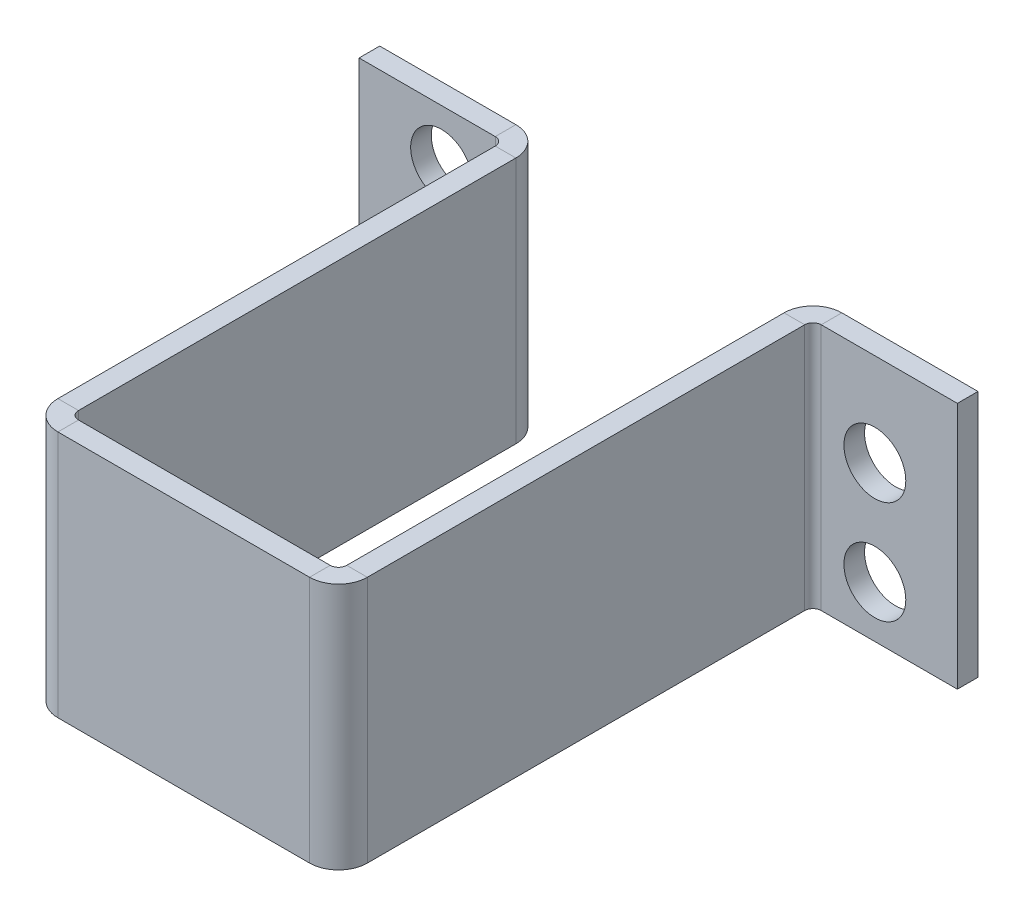
SolidWorks part; units mm, degrees
note: The reader was unsure of these and kept them because the rebuilt part matched: flange length of "Bordo-Flangia1", "Bordo-Flangia2".
ref_plane "Piano frontale" through (0, 0, 0) normal (0, 0, 1) x (1, 0, 0)
ref_plane "Piano superiore" through (0, 0, 0) normal (0, 1, 0) x (1, 0, 0)
ref_plane "Piano destro" through (0, 0, 0) normal (1, 0, 0) x (0, 0, -1)
sketch "Schizzo1" plane through (0, 0, 0) normal (0, 0, 1) x (1, 0, 0)
  line L1 (3.25, -3) -> (-3.25, -3)
  line L2 (3.25, -3) -> (3.25, 3)
  line L3 (3.25, 3) -> (-3.25, 3)
  line L4 (-3.25, -3) -> (-3.25, 3)
  line L5 (3.25, -3) -> (-3.25, 3) construction
  line L6 (3.25, 3) -> (-3.25, -3) construction
  point P0 (0, 0)
  dimension "D1" = 6
  dimension "D2" = 6.5
base flange "Base-Flangia1" sketch "Schizzo1" thickness 0.5 reverse thickness direction no parameters "D1"=0.7366
edge flange "Bordo-Flangia1" sketch "Schizzo10" flange profiles "Schizzo10", "Schizzo11" flange angle 90 flange length 11.5 flange position material outside bend radius 0.2 thickness 0.5 relief rectangular parameters "D6"=10, "D8"=1
sketch "Schizzo10" plane through (-3.25, 0, -0.5) normal (-1, 0, 0) x (0, 1, 0)
  line L0 (3, 0) -> (-3, 0) construction
  line L1 (3, 0) -> (-3, 0)
  line L2 (-3, 0) -> (-3, 11)
  line L3 (-3, 11) -> (3, 11)
  line L4 (3, 11) -> (3, 0)
sketch "Schizzo11" plane through (3.25, 0, -0.5) normal (1, 0, 0) x (0, -1, 0)
  line L0 (3, 0) -> (-3, 0) construction
  line L1 (3, 0) -> (-3, 0)
  line L2 (-3, 0) -> (-3, 11)
  line L3 (-3, 11) -> (3, 11)
  line L4 (3, 11) -> (3, 0)
bend "PiegaturaBordo1" bend radius 0.2 bend angle 90 parameters "D5"=1
bend "PiegaturaBordo2" bend radius 0.2 bend angle 90 parameters "D5"=2
edge flange "Bordo-Flangia2" sketch "Schizzo16" flange profiles "Schizzo16", "Schizzo17" flange angle 90 flange length 4 flange position material outside bend radius 0.2 thickness 0.5 relief rectangular parameters "D6"=10, "D8"=1
sketch "Schizzo16" plane through (-3.75, 0, -11.5) normal (0, 0, -1) x (0, -1, 0)
  line L0 (-3, 0) -> (3, 0) construction
  line L1 (-3, 0) -> (3, 0)
  line L2 (-3, 0) -> (-3, 3.5)
  line L3 (-3, 3.5) -> (3, 3.5)
  line L4 (3, 3.5) -> (3, 0)
sketch "Schizzo17" plane through (3.75, 0, -11.5) normal (0, 0, -1) x (0, 1, 0)
  line L0 (-3, 0) -> (3, 0) construction
  line L1 (-3, 0) -> (3, 0)
  line L2 (-3, 0) -> (-3, 3.5)
  line L3 (-3, 3.5) -> (3, 3.5)
  line L4 (3, 3.5) -> (3, 0)
bend "PiegaturaBordo3" bend radius 0.2 bend angle 90 parameters "D5"=3
bend "PiegaturaBordo4" bend radius 0.2 bend angle 90 parameters "D5"=4
sketch "Schizzo18" plane through (0, 0, -11.5) normal (0, 0, 1) x (1, 0, 0)
  line L0 (5.25, 3) -> (5.25, -3) construction
  line L4 (7.25, 3) -> (7.25, -3) construction
  line L5 (7.25, -3) -> (3.95, -3) construction
  circle A0 centre (5.25, 0.75) radius 0.75
  circle A1 centre (5.25, -1.75) radius 0.75
  point P2 (0, 0)
  point P5 (5.25, 1.3954)
  point P10 (0, 0)
  point P12 (0, 0)
  dimension "D1" = 1.5
  dimension "D2" = 1.5
  dimension "D3" = 1.25
  dimension "D4" = 2.5
  dimension "D5" = 2
extrude "Taglio-Estrusione1" cut sketch "Schizzo18" against normal through all normal cut yes
sketch "Schizzo22" plane through (0, 0, -11.5) normal (0, 0, 1) x (1, 0, 0)
  line L0 (-5.25, 3) -> (-5.25, -3) construction
  line L1 (-7.25, 3) -> (-3.95, 3) construction
  line L2 (-3.95, -3) -> (-7.25, -3) construction
  line L3 (-7.25, -3) -> (-7.25, 3) construction
  circle A0 centre (-5.25, 1.75) radius 0.75
  circle A1 centre (-5.25, -0.75) radius 0.75
  dimension "D2" = 1.5
  dimension "D3" = 1.5
  dimension "D1" = 2
  dimension "D4" = 2.25
  dimension "D5" = 2.5
extrude "Taglio-Estrusione2" cut sketch "Schizzo22" against normal through all normal cut yes
sketch "Linee di piegatura1" [suppressed] plane through (0, 0, 0) normal (0, 1, 0) x (1, 0, 0)
sketch "Casella di contorno1" [suppressed] plane through (0, 0, 0) normal (0, 1, 0) x (1, 0, 0)
sheet metal parameters "Lamiera1" thickness 0.5 parameters "D1"=0.7366
flat pattern "Ripetizione piatta1" [suppressed]
sketch "Linee di piegatura2" plane through (0, 0, 0) normal (0, 1, 0) x (1, 0, 0)
sketch3d "Casella di contorno2" [suppressed]
  line L0 (3.25, -3, 0) -> (-3.25, -3, 0) construction
  line L1 (3.25, 3, 0) -> (-3.25, 3, 0) construction
  line L2 (3.25, -3, 0) -> (3.25, 3, 0) construction
  line L3 (-3.25, -3, 0) -> (-3.25, 3, 0) construction
sheet metal parameters "Lamiera2" thickness 0.5 parameters "D1"=0.7366
flat pattern "Ripetizione piatta1"
sketch "Linee di piegatura2" plane through (0, 0, 0) normal (0, 0, 1) x (1, 0, 0)
  line L0 (3.4034, -3) -> (3.4034, 3) construction
  line L1 (-3.4034, 3) -> (-3.4034, -3) construction
  line L2 (3.4034, -3) -> (3.4034, 3) construction
  line L3 (-3.4034, 3) -> (-3.4034, -3) construction
sketch3d "Casella di contorno2" [suppressed]
  line L0 (-14.5569, -3, 0) -> (14.5569, -3, 0) construction
  line L1 (-14.5569, 3, 0) -> (14.5569, 3, 0) construction
  line L2 (-14.5569, -3, 0) -> (-14.5569, 3, 0) construction
  line L3 (14.5569, -3, 0) -> (14.5569, 3, 0) construction
bend of the flat pattern "Appiattito-<PiegaturaBordo1>1"
bend of the flat pattern "Appiattito-<PiegaturaBordo2>1"
sheet metal parameters "Lamiera3" thickness 0.5 parameters "D1"=0.7366
flat pattern "Ripetizione piatta1" [suppressed]
sketch "Linee di piegatura2" plane through (0, 0, 0) normal (0, 0, 1) x (1, 0, 0)
  line L0 (3.4034, -3) -> (3.4034, 3) construction
  line L1 (-3.4034, 3) -> (-3.4034, -3) construction
  line L2 (3.4034, -3) -> (3.4034, 3) construction
  line L3 (-3.4034, 3) -> (-3.4034, -3) construction
  line L4 (14.603, -3) -> (14.603, 3) construction
  line L5 (-14.603, 3) -> (-14.603, -3) construction
  line L6 (14.603, -3) -> (14.603, 3) construction
  line L7 (-14.603, 3) -> (-14.603, -3) construction
sketch3d "Casella di contorno2" [suppressed]
  line L0 (-18.1491, -3, 0) -> (18.1491, -3, 0) construction
  line L1 (-18.1491, 3, 0) -> (18.1491, 3, 0) construction
  line L2 (-18.1491, -3, 0) -> (-18.1491, 3, 0) construction
  line L3 (18.1491, -3, 0) -> (18.1491, 3, 0) construction
bend of the flat pattern "Appiattito-<PiegaturaBordo1>1"
bend of the flat pattern "Appiattito-<PiegaturaBordo2>1"
bend of the flat pattern "Appiattito-<PiegaturaBordo3>1"
bend of the flat pattern "Appiattito-<PiegaturaBordo4>1"
sketch "Schizzo18-1" [suppressed] plane through (10.8991, 0, 0) normal (0, 0, 1) x (1, 0, 0)
  line L0 (5.25, 3) -> (5.25, -3) construction
  line L4 (7.25, 3) -> (7.25, -3) construction
  circle A0 centre (5.25, 0.75) radius 0.75
  circle A1 centre (5.25, -1.75) radius 0.75
  dimension "D1" = 1.5
  dimension "D2" = 1.5
  dimension "D3" = 1.25
  dimension "D4" = 2.5
  dimension "D5" = 2
sheet metal parameters "Lamiera4" thickness 0.5 parameters "D1"=0.7366
flat pattern "Ripetizione piatta1" [suppressed]
sketch "Linee di piegatura2" plane through (0, 0, 0) normal (0, 0, 1) x (1, 0, 0)
  line L0 (3.4034, -3) -> (3.4034, 3) construction
  line L1 (-3.4034, 3) -> (-3.4034, -3) construction
  line L2 (3.4034, -3) -> (3.4034, 3) construction
  line L3 (-3.4034, 3) -> (-3.4034, -3) construction
  line L4 (14.7103, -3) -> (14.7103, 3) construction
  line L5 (-14.7103, 3) -> (-14.7103, -3) construction
  line L6 (14.7103, -3) -> (14.7103, 3) construction
  line L7 (-14.7103, 3) -> (-14.7103, -3) construction
sketch3d "Casella di contorno2" [suppressed]
  line L0 (-18.3637, -3, 0) -> (18.3637, -3, 0) construction
  line L1 (-18.3637, 3, 0) -> (18.3637, 3, 0) construction
  line L2 (-18.3637, -3, 0) -> (-18.3637, 3, 0) construction
  line L3 (18.3637, -3, 0) -> (18.3637, 3, 0) construction
bend of the flat pattern "Appiattito-<PiegaturaBordo1>1"
bend of the flat pattern "Appiattito-<PiegaturaBordo2>1"
bend of the flat pattern "Appiattito-<PiegaturaBordo3>1"
bend of the flat pattern "Appiattito-<PiegaturaBordo4>1"
sketch "Schizzo18-1" [suppressed] plane through (11.1137, 0, 0) normal (0, 0, 1) x (1, 0, 0)
  line L0 (5.25, 3) -> (5.25, -3) construction
  line L4 (7.25, 3) -> (7.25, -3) construction
  circle A0 centre (5.25, 0.75) radius 0.75
  circle A1 centre (5.25, -1.75) radius 0.75
  dimension "D1" = 1.5
  dimension "D2" = 1.5
  dimension "D3" = 1.25
  dimension "D4" = 2.5
  dimension "D5" = 2
sheet metal parameters "Lamiera5" thickness 0.5 parameters "D1"=0.7366
flat pattern "Ripetizione piatta1" [suppressed]
sketch "Linee di piegatura2" plane through (0, 0, 0) normal (0, 0, 1) x (1, 0, 0)
  line L0 (3.4034, -3) -> (3.4034, 3) construction
  line L1 (-3.4034, 3) -> (-3.4034, -3) construction
  line L2 (3.4034, -3) -> (3.4034, 3) construction
  line L3 (-3.4034, 3) -> (-3.4034, -3) construction
  line L4 (14.7103, -3) -> (14.7103, 3) construction
  line L5 (-14.7103, 3) -> (-14.7103, -3) construction
  line L6 (14.7103, -3) -> (14.7103, 3) construction
  line L7 (-14.7103, 3) -> (-14.7103, -3) construction
sketch3d "Casella di contorno2" [suppressed]
  line L0 (-18.3637, -3, 0) -> (18.3637, -3, 0) construction
  line L1 (-18.3637, 3, 0) -> (18.3637, 3, 0) construction
  line L2 (-18.3637, -3, 0) -> (-18.3637, 3, 0) construction
  line L3 (18.3637, -3, 0) -> (18.3637, 3, 0) construction
bend of the flat pattern "Appiattito-<PiegaturaBordo1>1"
bend of the flat pattern "Appiattito-<PiegaturaBordo2>1"
bend of the flat pattern "Appiattito-<PiegaturaBordo3>1"
bend of the flat pattern "Appiattito-<PiegaturaBordo4>1"
sketch "Schizzo18-1" plane through (11.1137, 0, 0) normal (0, 0, 1) x (1, 0, 0)
  line L0 (5.25, 3) -> (5.25, -3) construction
  line L4 (7.25, 3) -> (7.25, -3) construction
  circle A0 centre (5.25, 0.75) radius 0.75
  circle A1 centre (5.25, -1.75) radius 0.75
  dimension "D1" = 1.5
  dimension "D2" = 1.5
  dimension "D3" = 1.25
  dimension "D4" = 2.5
  dimension "D5" = 2
